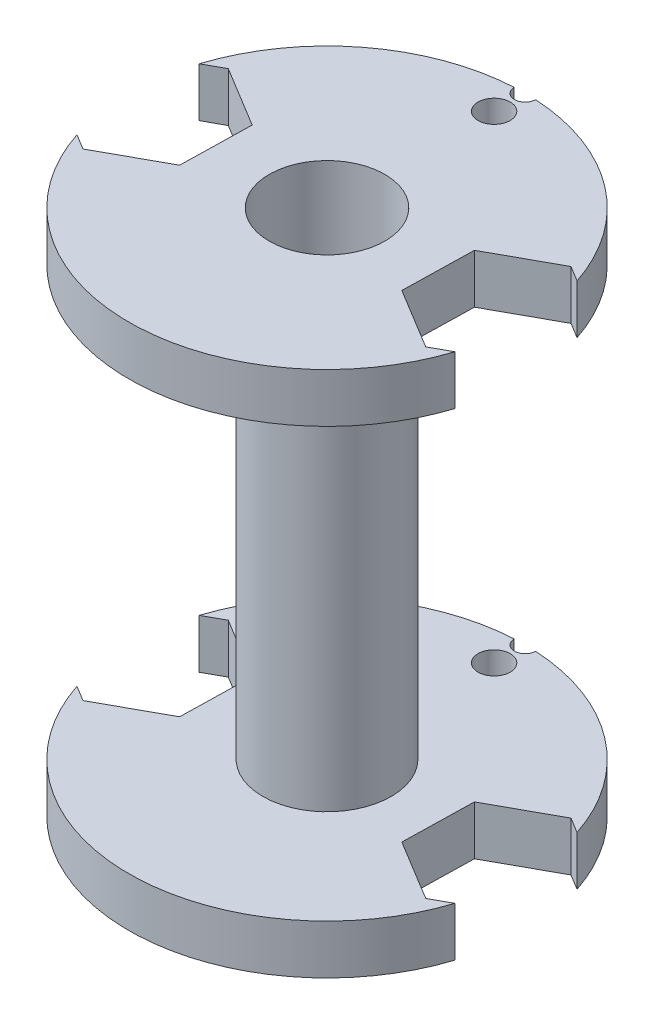
SolidWorks part; units mm, degrees
ref_plane "Front Plane" through (0, 0, 0) normal (0, 0, 1) x (1, 0, 0)
ref_plane "Top Plane" through (0, 0, 0) normal (0, 1, 0) x (1, 0, 0)
ref_plane "Right Plane" through (0, 0, 0) normal (1, 0, 0) x (0, 0, -1)
sketch "Sketch1" plane through (0, 0, 0) normal (0, 1, 0) x (1, 0, 0)
  circle A1 centre (0, 0) radius 9.25
  circle A2 centre (0, 0) radius 2.7
extrude "Boss-Extrude1" add sketch "Sketch1" along normal blind 2.3
sketch "Sketch2" plane through (0, 2.3, 0) normal (0, 1, 0) x (1, 0, 0)
  circle A0 centre (0, 0) radius 3
  circle A1 centre (0, 0) radius 2.7
sketch "Sketch3" plane through (0, 0, 0) normal (0, -1, 0) x (1, 0, 0)
  line L0 (-5.1613, 1.7213) -> (-8.0713, 3.319)
  line L1 (5.1613, -1.7213) -> (8.0713, -3.319)
  line L2 (8.0713, -3.319) -> (10.91, -1.5977)
  line L3 (10.91, -1.5977) -> (10.8387, 1.7213)
  line L4 (10.8387, 1.7213) -> (7.9287, 3.319)
  line L5 (7.9287, 3.319) -> (5.09, 1.5977)
  line L6 (5.09, 1.5977) -> (5.1613, -1.7213)
  line L7 (-8.0713, 3.319) -> (-10.91, 1.5977)
  line L8 (-10.91, 1.5977) -> (-10.8387, -1.7213)
  line L9 (-10.8387, -1.7213) -> (-7.9287, -3.319)
  line L10 (-7.9287, -3.319) -> (-5.09, -1.5977)
  line L11 (-5.09, -1.5977) -> (-5.1613, 1.7213)
  circle A0 centre (8, 0) radius 2.875 construction
  point P17 (0, 0)
  dimension "D2" = 8
  dimension "D1" = 2
extrude "Cut-Extrude3" cut sketch "Sketch3" against normal blind 2.5
sketch "Sketch4" plane through (0, 2.3, 0) normal (0, 1, 0) x (1, 0, 0)
  circle A0 centre (0, 7.8) radius 0.75
  circle A1 centre (0, 9.25) radius 0.5
  circle A2 centre (0, 0) radius 9.25 construction
  dimension "D1" = 7.8
extrude "Cut-Extrude4" cut sketch "Sketch4" against normal blind 5
sketch "Sketch5" plane through (0, 2.3, 0) normal (0, 1, 0) x (1, 0, 0)
  circle A0 centre (0, -16.2068) radius 3.1
extrude "Cut-Extrude5" [suppressed] cut sketch "Sketch5" along normal blind 2.5 from surface
extrude "Boss-Extrude2" add sketch "Sketch2" along normal blind 10
mirror "Mirror7" about plane through (0, 12.3, 0) normal (0, 1, 0) of bodies 107
